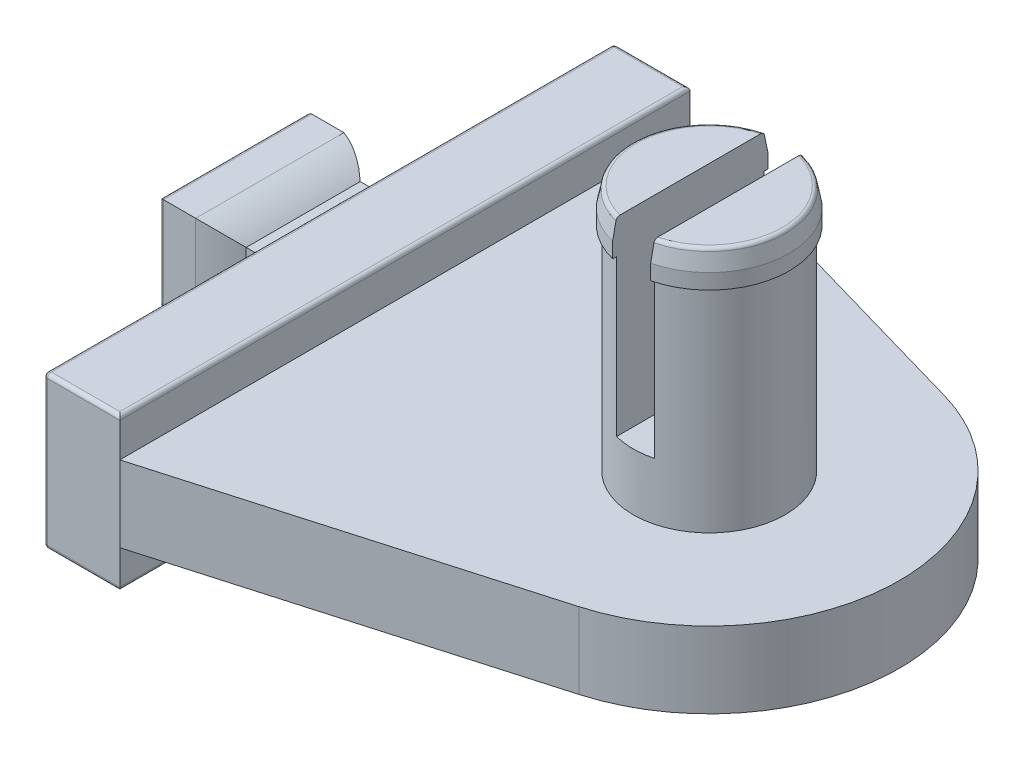
SolidWorks part; units mm, degrees
ref_plane "前视基准面" through (0, 0, 0) normal (0, 0, 1) x (1, 0, 0)
ref_plane "上视基准面" through (0, 0, 0) normal (0, 1, 0) x (1, 0, 0)
ref_plane "右视基准面" through (0, 0, 0) normal (1, 0, 0) x (0, 0, -1)
sketch "草图1" plane through (0, 0, 0) normal (0, 1, 0) x (1, 0, 0)
  line L0 (0, 0) -> (15, 0) construction
  line L1 (15, 0) -> (10, 0) construction
  line L2 (0, -7.5) -> (0, 7.5)
  line L3 (0, 7.5) -> (2, 7.5)
  line L4 (0, -7.5) -> (2, -7.5)
  line L5 (2, 7.5) -> (11.3803, 4.8057)
  line L6 (2, -7.5) -> (11.3803, -4.8057)
  arc A0 (11.3803, -4.8057) -> (11.3803, 4.8057) centre (10, 0) ccw
  dimension "D1" = 15
  dimension "D2" = 5
  dimension "D3" = 7.5
  dimension "D4" = 2
extrude "凸台-拉伸1" add sketch "草图1" along normal blind 1 and the other way blind 1
sketch "草图3" plane through (0, 1, 0) normal (0, 1, 0) x (1, 0, 0)
  line L0 (2, 7.5) -> (2, -7.5)
  line L5 (0, -7.5) -> (2, -7.5)
  line L6 (2, -7.5) -> (11.3803, -4.8057)
  line L7 (11.3803, 4.8057) -> (2, 7.5)
  line L8 (2, 7.5) -> (0, 7.5)
  line L9 (0, 7.5) -> (0, -7.5)
  line L10 (0, -7.5) -> (2, -7.5)
  line L13 (2, 7.5) -> (0, 7.5)
  line L14 (0, 7.5) -> (0, -7.5)
  arc A1 (11.3803, -4.8057) -> (11.3803, 4.8057) centre (10, 0) ccw
  dimension "D1" = 0
extrude "凸台-拉伸2" add sketch "草图3" along normal blind 1
mirror "镜向1" about plane through (0, 0, 0) normal (0, 1, 0) of "凸台-拉伸2"
sketch "草图4" plane through (0, 1, 0) normal (0, 1, 0) x (1, 0, 0)
  line L0 (0, 0) -> (10, 0) construction
  circle A0 centre (10, 0) radius 2
  dimension "D2" = 4
  dimension "D1" = 10
extrude "凸台-拉伸3" add sketch "草图4" along normal blind 6.5
sketch "草图5" plane through (0, 0, 0) normal (0, 0, 1) x (1, 0, 0)
  line L0 (10, 7.5) -> (10, 1.0211) construction
  line L1 (12, 7.5) -> (8, 7.5) construction
  line L2 (8, 7.5) -> (8, 6.6)
  line L3 (8, 6.6) -> (7.9, 6.6)
  line L4 (7.9, 6.6) -> (7.9, 7)
  line L5 (7.9, 7) -> (8, 7.5)
  dimension "D1" = 0.9
  dimension "D2" = 0.1
  dimension "D3" = 0.4
revolve "旋转1" add sketch "草图5" angle 360 about L0
sketch "草图6" plane through (0, 7.5, 0) normal (0, 1, 0) x (1, 0, 0)
  line L0 (10, 0) -> (10.5, 0) construction
  line L1 (10.5, -3) -> (10.5, 3)
  line L2 (10.5, 3) -> (9.5, 3)
  line L3 (10, 3) -> (10, 0) construction
  line L4 (10.5, -3) -> (9.5, -3)
  line L5 (9.5, -3) -> (9.5, 3)
  point P9 (10, -3)
  dimension "D1" = 0.5
  dimension "D2" = 3
extrude "切除-拉伸1" cut sketch "草图6" against normal blind 5
sketch "草图7" plane through (0, 0, 0) normal (0, 1, 0) x (1, 0, 0)
  line L0 (0, 0) -> (-2, 0) construction
  line L1 (0, 7.5) -> (0, -7.5) construction
  line L2 (-2, 0) -> (-2.5, 0) construction
  line L3 (0, -1.5) -> (0, 1.5)
  line L4 (0, 1.5) -> (-0.6771, 1.5)
  line L5 (-2.5, -1.95) -> (-2.5, 1.95)
  line L6 (-2.5, 1.95) -> (-1.5556, 1.95)
  line L7 (0, -1.5) -> (-0.6771, -1.5)
  line L8 (-2.5, -1.95) -> (-1.5556, -1.95)
  arc A0 (-0.6771, 1.5) -> (-1.5556, 1.95) centre (-2, 0) ccw
  arc A1 (-0.6771, -1.5) -> (-1.5556, -1.95) centre (-2, 0) cw
  dimension "D1" = 2
  dimension "D2" = 0.5
  dimension "D3" = 1.5
  dimension "D4" = 1.95
extrude "凸台-拉伸4" add sketch "草图7" along normal blind 3 and the other way blind 3
sketch "草图8" plane through (0, 0, 0) normal (0, 0, 1) x (1, 0, 0)
  line L0 (0, 0) -> (-2, 0) construction
  line L1 (-2, 0) -> (-2.5, 0) construction
  line L2 (-2.5, -3) -> (-2.5, 3) construction
  line L3 (0, -3) -> (0, -1.5)
  line L4 (0, -2) -> (0, 2) construction
  line L5 (0, 1.5) -> (-0.6771, 1.5)
  line L6 (-2.5, 3) -> (0, 3)
  line L7 (-2.5, 1.95) -> (-1.5556, 1.95)
  line L8 (-2.5, 3) -> (-2.5, 1.95)
  line L9 (0, -1.5) -> (-0.6771, -1.5)
  line L10 (0, 3) -> (0, 1.5)
  line L11 (-2.5, -1.95) -> (-1.5556, -1.95)
  line L12 (-2.5, -3) -> (-2.5, -1.95)
  line L13 (-2.5, -3) -> (0, -3)
  arc A0 (-0.6771, 1.5) -> (-1.5556, 1.95) centre (-2, 0) ccw
  arc A1 (-0.6771, -1.5) -> (-1.5556, -1.95) centre (-2, 0) cw
  dimension "D1" = 2
  dimension "D2" = 1.5
  dimension "D3" = 1.95
extrude "切除-拉伸2" cut sketch "草图8" against normal blind 5 and the other way blind 5
fillet "圆角2" radius 0.1 6 edges at (-2.5, 0, 1.95) (-2.5, -1.95, 0) (-2.5, 0, -1.95) (-2.5, 1.95, 0) (8, 7.5, 0) (12, 7.5, 0)
fillet "圆角4" radius 0.1 10 edges at (1, -2, -7.5) (2, -2, 0) (1, -2, 7.5) (2, 2, 0) (1, 2, 7.5) (1, 2, -7.5) (0, 0, -7.5) (0, 0, 7.5) (0, -2, 0) (0, 2, 0)
